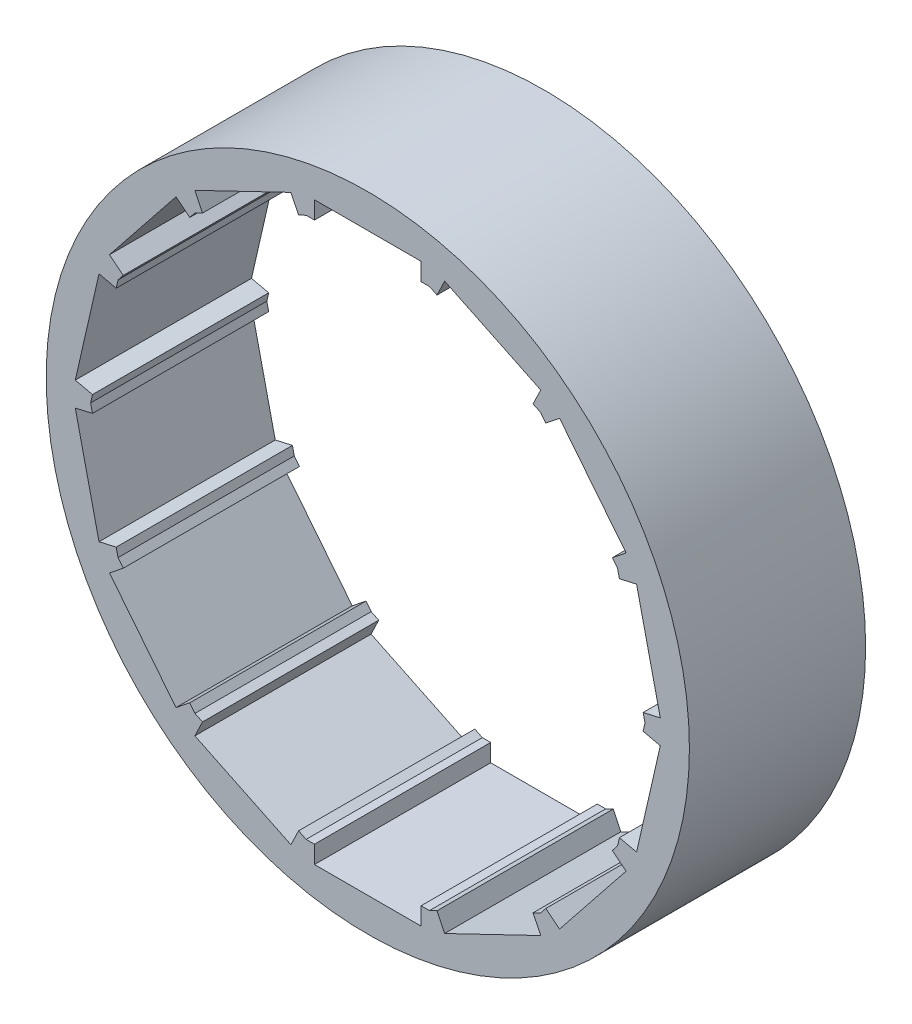
SolidWorks part; units mm, degrees
ref_plane "正面" through (0, 0, 0) normal (0, 0, 1) x (1, 0, 0)
ref_plane "平面" through (0, 0, 0) normal (0, 1, 0) x (1, 0, 0)
ref_plane "右側面" through (0, 0, 0) normal (1, 0, 0) x (0, 0, -1)
sketch "ｽｹｯﾁ1" plane through (0, 0, 0) normal (0, 0, 1) x (1, 0, 0)
  line L0 (36.5863, 0) -> (32.9631, 15.8742) construction
  line L1 (31.4577, 0) -> (28.3424, 13.649)
  line L2 (28.3424, 13.649) -> (19.6136, 24.5946)
  line L3 (19.6136, 24.5946) -> (7, 30.669)
  line L4 (7, 30.669) -> (-7, 30.669)
  line L5 (-7, 30.669) -> (-19.6136, 24.5946)
  line L6 (-19.6136, 24.5946) -> (-28.3424, 13.649)
  line L7 (-28.3424, 13.649) -> (-31.4577, 0)
  line L8 (-31.4577, 0) -> (-28.3424, -13.649)
  line L9 (-28.3424, -13.649) -> (-19.6136, -24.5946)
  line L10 (-19.6136, -24.5946) -> (-7, -30.669)
  line L11 (-7, -30.669) -> (7, -30.669)
  line L12 (7, -30.669) -> (19.6136, -24.5946)
  line L13 (19.6136, -24.5946) -> (28.3424, -13.649)
  line L14 (28.3424, -13.649) -> (31.4577, 0)
  line L15 (32.9631, 15.8742) -> (22.8112, 28.6043) construction
  line L16 (22.8112, 28.6043) -> (8.1412, 35.669) construction
  line L17 (8.1412, 35.669) -> (-8.1412, 35.669) construction
  line L18 (-8.1412, 35.669) -> (-22.8112, 28.6043) construction
  line L19 (-22.8112, 28.6043) -> (-32.9631, 15.8742) construction
  line L20 (-32.9631, 15.8742) -> (-36.5863, 0) construction
  line L21 (-36.5863, 0) -> (-32.9631, -15.8742) construction
  line L22 (-32.9631, -15.8742) -> (-22.8112, -28.6043) construction
  line L23 (-22.8112, -28.6043) -> (-8.1412, -35.669) construction
  line L24 (-8.1412, -35.669) -> (8.1412, -35.669) construction
  line L25 (8.1412, -35.669) -> (22.8112, -28.6043) construction
  line L26 (22.8112, -28.6043) -> (32.9631, -15.8742) construction
  line L27 (32.9631, -15.8742) -> (36.5863, 0) construction
  circle A0 centre (0, 0) radius 30.669 construction
  circle A1 centre (0, 0) radius 36.5
  dimension "D3" = 73
  dimension "D1" = 14
  dimension "D2" = 5
extrude "ﾎﾞｽ - 押し出し1" add sketch "ｽｹｯﾁ1" along normal blind 20
ref_axis "軸1" through (0, 0, 0) along (0, 0, 1)
sketch "ｽｹｯﾁ3" plane through (0, 0, 20) normal (0, 0, 1) x (1, 0, 0)
  line L0 (0, 0) -> (0, 33.0954) construction
  line L1 (7, 30.669) -> (-7, 30.669) construction
  line L2 (-6.05, 32.669) -> (6.05, 32.669)
  line L3 (-6.05, 32.669) -> (-6.05, 30.669)
  line L4 (-6.05, 30.669) -> (6.05, 30.669)
  line L5 (6.05, 32.669) -> (6.05, 30.669)
  line L6 (-6.05, 32.669) -> (6.05, 30.669) construction
  line L7 (-6.05, 30.669) -> (6.05, 32.669) construction
  point P3 (0, 31.669)
  dimension "D1" = 2
  dimension "D2" = 12.1
extrude "ｶｯﾄ - 押し出し2" cut sketch "ｽｹｯﾁ3" against normal through all
pattern_circular "円形ﾊﾟﾀｰﾝ2" count 14 over 360 about axis through (0, 0, 0) along (0, 0, 1) of "ｶｯﾄ - 押し出し2"
